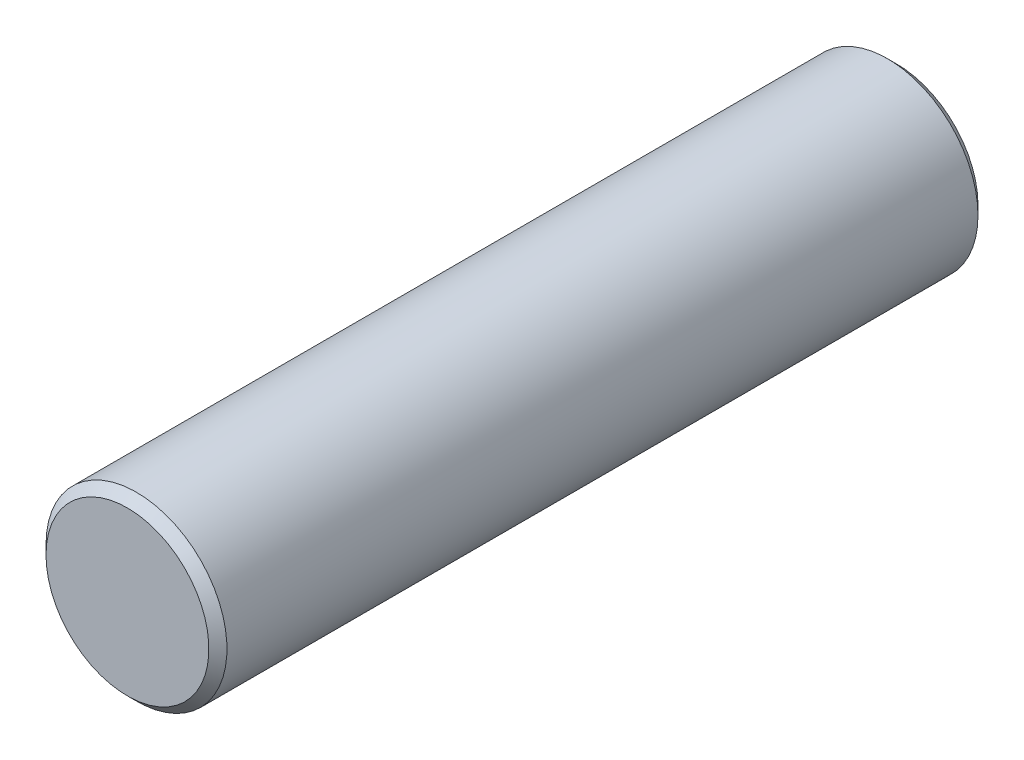
SolidWorks part; units mm, degrees
ref_plane "Front Plane" through (0, 0, 0) normal (0, 0, 1) x (1, 0, 0)
ref_plane "Top Plane" through (0, 0, 0) normal (0, 1, 0) x (1, 0, 0)
ref_plane "Right Plane" through (0, 0, 0) normal (1, 0, 0) x (0, 0, -1)
sketch "Sketch1" plane through (0, 0, 0) normal (0, 1, 0) x (1, 0, 0)
  line L1 (10, 85) -> (0, 85)
  line L2 (10, 85) -> (10, 0)
  line L3 (10, 0) -> (0, 0)
  line L4 (0, 85) -> (0, 0)
  line L5 (10, 85) -> (0, 0) construction
  line L6 (10, 0) -> (0, 85) construction
  point P0 (5, 42.5)
  dimension "D1" = 10
  dimension "D2" = 85
revolve "Revolve1" add sketch "Sketch1" angle 360 about L4
ref_axis "Axis1" through (0, 0, 0) along (0, 0, -1)
chamfer "Chamfer1" distance 1 angle 45 2 edges at (-10, 0, -85) (-10, 0, 0)
sketch "Sketch2" plane through (0, 0, -85) normal (0, 0, -1) x (-1, 0, 0)
  circle A0 centre (0, 0) radius 0.5
  dimension "D1" = 1
extrude "Cut-Extrude1" cut sketch "Sketch2" against normal blind 3
